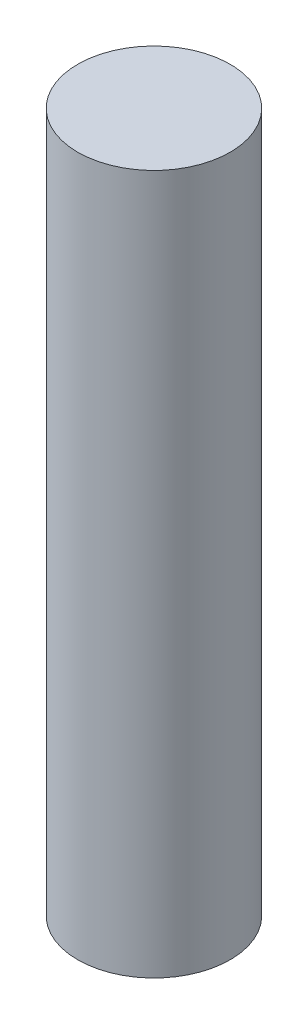
SolidWorks part; units mm, degrees
ref_plane "Front Plane" through (0, 0, 0) normal (0, 0, 1) x (1, 0, 0)
ref_plane "Top Plane" through (0, 0, 0) normal (0, 1, 0) x (1, 0, 0)
ref_plane "Right Plane" through (0, 0, 0) normal (1, 0, 0) x (0, 0, -1)
sketch "Sketch1" plane through (0, 0, 0) normal (0, 1, 0) x (1, 0, 0)
  circle A0 centre (0, 0) radius 1
  dimension "D1" = 2
extrude "Boss-Extrude1" add sketch "Sketch1" along normal blind 9.175
